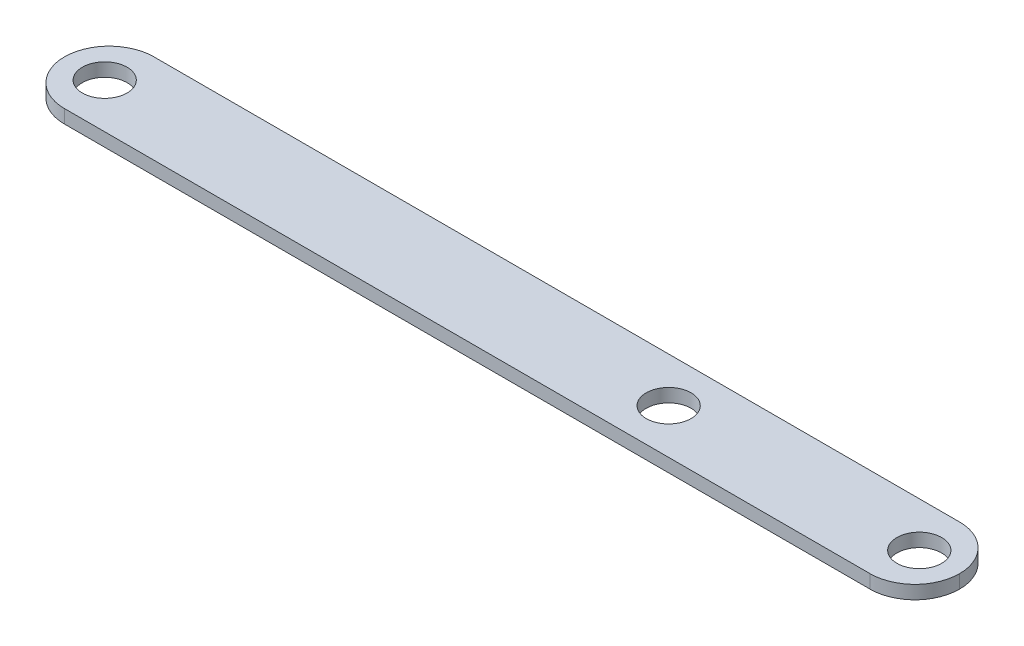
SolidWorks part; units mm, degrees
ref_plane "Front Plane" through (0, 0, 0) normal (0, 0, 1) x (1, 0, 0)
ref_plane "Top Plane" through (0, 0, 0) normal (0, 1, 0) x (1, 0, 0)
ref_plane "Right Plane" through (0, 0, 0) normal (1, 0, 0) x (0, 0, -1)
sketch "Sketch2" plane through (0, 0, 0) normal (0, 1, 0) x (1, 0, 0)
  line L1 (0, 0) -> (200, 0)
  line L2 (0, 0) -> (0, 20)
  line L3 (0, 20) -> (200, 20)
  line L4 (200, 0) -> (200, 20)
  dimension "D1" = 200
  dimension "D2" = 20
extrude "Boss-Extrude1" add sketch "Sketch2" along normal blind 3
sketch "Sketch3" plane through (0, 3, 0) normal (0, 1, 0) x (1, 0, 0)
  line L0 (200, 20) -> (0, 20) construction
  line L1 (0, 20) -> (0, 0) construction
  circle A0 centre (9, 10) radius 5
  dimension "D1" = 10
  dimension "D2" = 9
extrude "Cut-Extrude1" cut sketch "Sketch3" against normal through all
sketch "Sketch4" plane through (0, 3, 0) normal (0, 1, 0) x (1, 0, 0)
  line L0 (200, 20) -> (0, 20) construction
  line L1 (200, 0) -> (200, 20) construction
  circle A0 centre (191, 10) radius 5
  dimension "D1" = 10
  dimension "D2" = 9
extrude "Cut-Extrude2" cut sketch "Sketch4" against normal through all
fillet "Fillet1" radius 10 2 edges at (0, 1.5, -20) (0, 1.5, 0)
fillet "Fillet2" radius 10 2 edges at (200, 1.5, -20) (200, 1.5, 0)
sketch "Sketch5" plane through (0, 3, 0) normal (0, 1, 0) x (1, 0, 0)
  line L0 (10, 0) -> (190, 0) construction
  circle A0 centre (135, 10) radius 5
  point P6 (100, 0)
  dimension "D1" = 135
  dimension "D2" = 10
extrude "Cut-Extrude3" cut sketch "Sketch5" against normal through all
